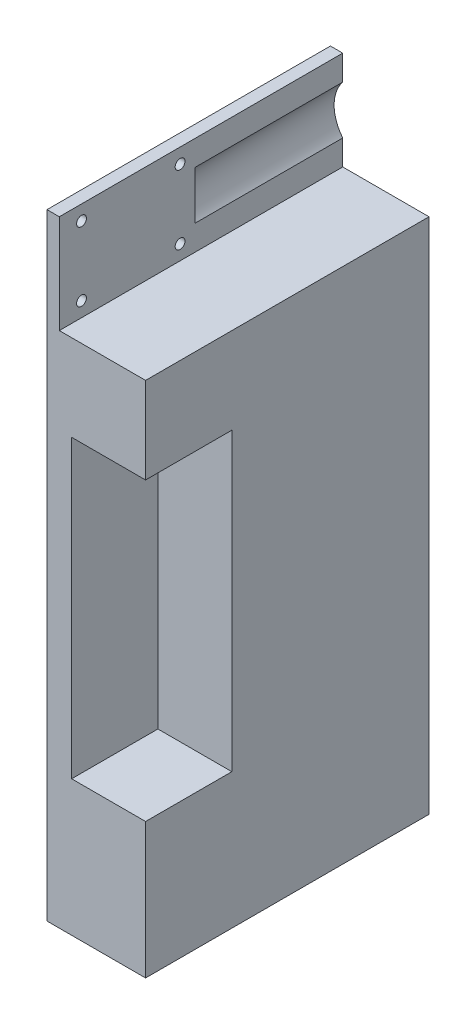
SolidWorks part; units mm, degrees
ref_plane "Front Plane" through (0, 0, 0) normal (0, 0, 1) x (1, 0, 0)
ref_plane "Top Plane" through (0, 0, 0) normal (0, 1, 0) x (1, 0, 0)
ref_plane "Right Plane" through (0, 0, 0) normal (1, 0, 0) x (0, 0, -1)
sketch "Sketch1" plane through (0, 0, 0) normal (0, 0, 1) x (1, 0, 0)
  line L0 (0, 0) -> (0, 40)
  line L1 (0, 40) -> (-5, 40)
  line L2 (-5, 40) -> (-5, -210)
  line L3 (-5, -210) -> (35, -210)
  line L4 (35, -210) -> (35, 0)
  line L5 (0, 0) -> (35, 0)
  dimension "D1" = 5
  dimension "D2" = 40
  dimension "D3" = 250
  dimension "D4" = 35
extrude "Boss-Extrude1" add sketch "Sketch1" along normal blind 115
sketch "Sketch2" plane through (-5, 0, 0) normal (-1, 0, 0) x (0, 0, 1)
  line L0 (106, 40) -> (106, 34) construction
  line L1 (115, 40) -> (0, 40) construction
  line L2 (115, 40) -> (115, -210) construction
  line L3 (106, 34) -> (66, 34) construction
  line L4 (106, 34) -> (106, 20) construction
  line L5 (106, 20) -> (115, 20) construction
  circle A0 centre (106, 34) radius 2
  circle A1 centre (66, 34) radius 2
  circle A2 centre (66, 6) radius 2
  circle A3 centre (106, 6) radius 2
  dimension "D4" = 4
  dimension "D5" = 4
  dimension "D1" = 6
  dimension "D2" = 9
  dimension "D3" = 40
  dimension "D6" = 28
extrude "Cut-Extrude1" cut sketch "Sketch2" against normal through all
sketch "Sketch3" plane through (0, 0, 0) normal (0, 0, -1) x (-1, 0, 0)
  line L0 (0, 36) -> (0, 32) construction
  line L2 (0, 40) -> (5, 40) construction
  circle A0 centre (-12, 20) radius 15.5
  dimension "D3" = 31
  dimension "D1" = 12
  dimension "D2" = 20
extrude "Cut-Extrude2" cut sketch "Sketch3" against normal blind 60
sketch "Sketch4" plane through (35, 0, 0) normal (1, 0, 0) x (0, 0, -1)
  line L0 (-115, -210) -> (-115, 0) construction
  line L1 (-115, -35) -> (-80, -35)
  line L2 (-115, -35) -> (-115, -155)
  line L3 (-115, -155) -> (-80, -155)
  line L4 (-80, -35) -> (-80, -155)
  line L5 (0, -210) -> (0, 0) construction
  line L6 (-115, 0) -> (0, 0) construction
  dimension "D1" = 80
  dimension "D2" = 35
  dimension "D3" = 120
extrude "Cut-Extrude3" cut sketch "Sketch4" against normal blind 30
